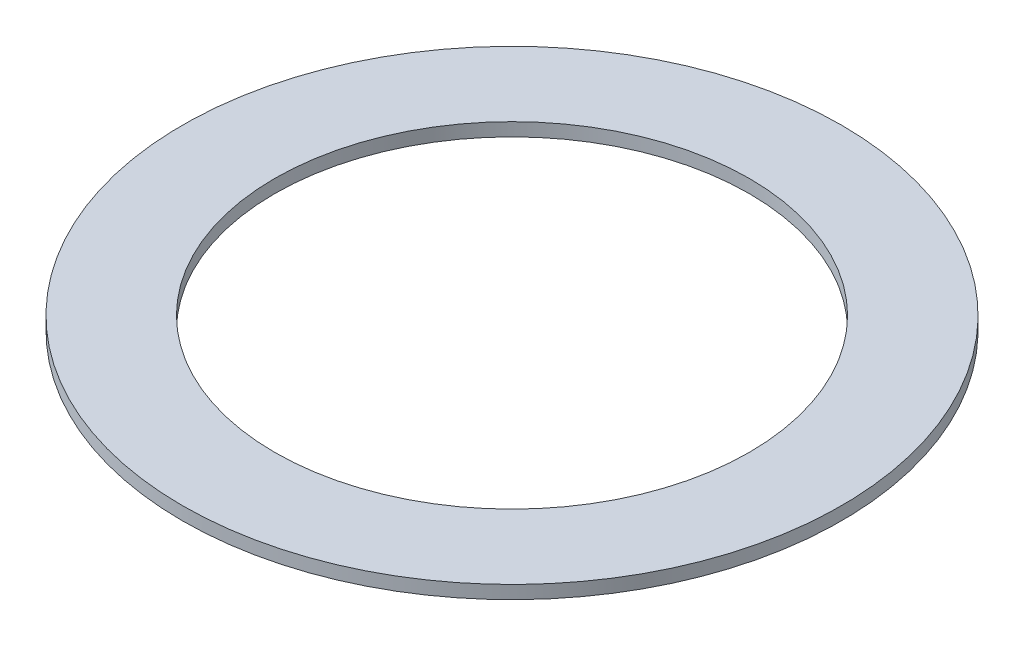
SolidWorks part; units mm, degrees
ref_plane "Front Plane" through (0, 0, 0) normal (0, 0, 1) x (1, 0, 0)
ref_plane "Top Plane" through (0, 0, 0) normal (0, 1, 0) x (1, 0, 0)
ref_plane "Right Plane" through (0, 0, 0) normal (1, 0, 0) x (0, 0, -1)
sketch "Sketch1" plane through (0, 0, 0) normal (0, 1, 0) x (1, 0, 0)
  line L0 (-12.5, 0) -> (12.5, 0) construction
  circle A0 centre (0, 0) radius 12.5 construction
  circle A1 centre (0, 0) radius 9 construction
  point P6 (-9, 0)
  point P7 (9, 0)
  point P8 (0, -12.5)
  point P9 (0, 12.5)
  dimension "OD" = 25
  dimension "ID" = 18
sketch "Sketch2" plane through (0, 0, 0) normal (1, 0, 0) x (0, 0, -1)
  line L1 (-12.5, 0.25) -> (12.5, 0.25) construction
  line L2 (-12.5, 0.25) -> (-12.5, -0.25) construction
  line L3 (-12.5, -0.25) -> (12.5, -0.25) construction
  line L4 (12.5, 0.25) -> (12.5, -0.25) construction
  dimension "Thickness" = 0.5
sketch "Sketch3" plane through (0, 0, 0) normal (0, 1, 0) x (1, 0, 0)
  circle A0 centre (0, 0) radius 12.5
  circle A1 centre (0, 0) radius 9
extrude "Boss-Extrude1" add sketch "Sketch3" along normal up to vertex (0.25 mm away) and the other way up to vertex (0.25 mm away) up to point (0, 0.25, -12.5) other way up to point (0, -0.25, -12.5)
